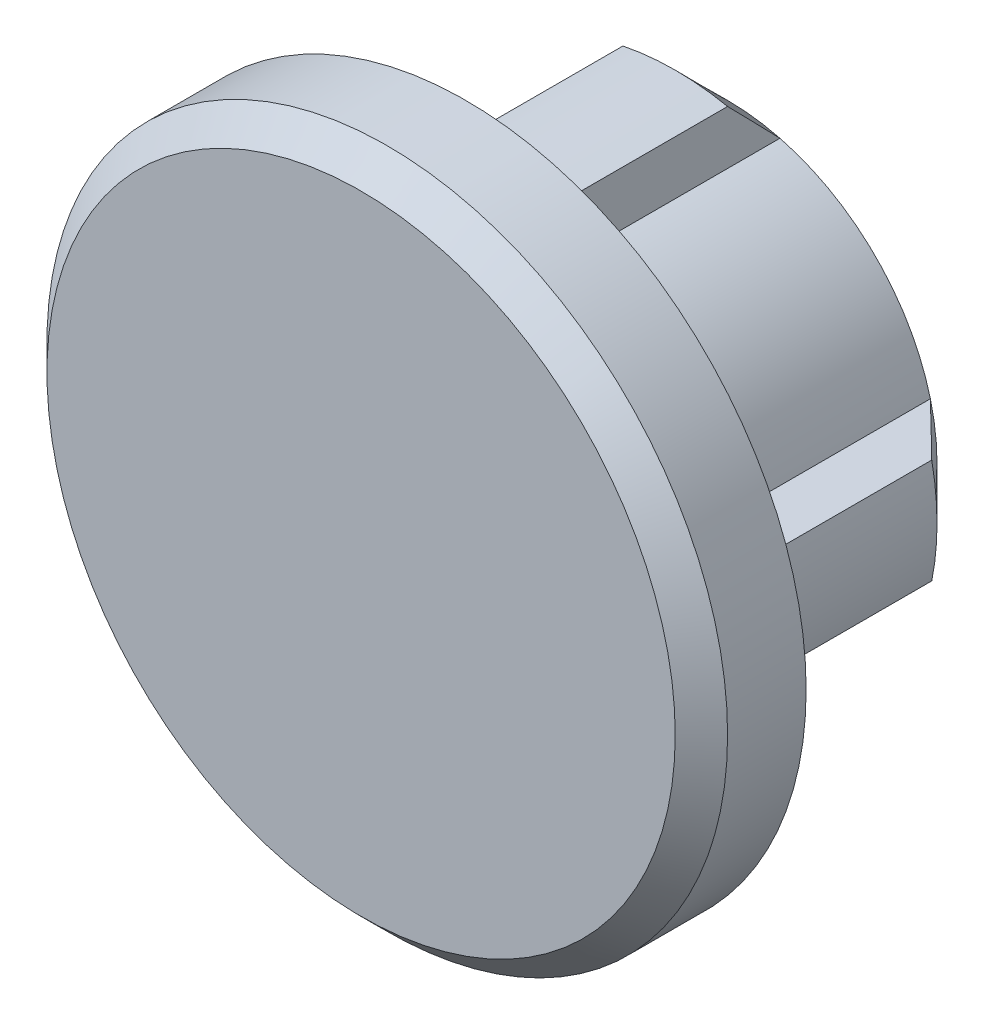
SolidWorks part; units mm, degrees
ref_plane "Front Plane" through (0, 0, 0) normal (0, 0, 1) x (1, 0, 0)
ref_plane "Top Plane" through (0, 0, 0) normal (0, 1, 0) x (1, 0, 0)
ref_plane "Right Plane" through (0, 0, 0) normal (1, 0, 0) x (0, 0, -1)
sketch "Sketch1" plane through (0, 0, 0) normal (0, 0, 1) x (1, 0, 0)
  circle A0 centre (0, 0) radius 2.5
  circle A1 centre (0, 0) radius 5
  dimension "D1" = 10
  dimension "D2" = 5
extrude "Boss-Extrude1" add sketch "Sketch1" against normal blind 5
sketch "Sketch2" plane through (0, 0, 0) normal (0, 0, 1) x (1, 0, 0)
  circle A0 centre (0, 0) radius 6.5
  dimension "D1" = 13
extrude "Boss-Extrude2" add sketch "Sketch2" along normal blind 2
chamfer "Chamfer1" distance 0.5 angle 45 1 edges at (6.5, 0, 2)
sketch "Sketch3" plane through (0, 0, 0) normal (0, 0, -1) x (-1, 0, 0)
  line L0 (3.85, 0) -> (-3.85, 0) construction
  line L1 (4.5826, 2) -> (6.1847, 2)
  line L3 (4.5826, -2) -> (6.1847, -2)
  circle A0 centre (0, 0) radius 5 construction
  circle A1 centre (0, 0) radius 6.5 construction
  circle A2 centre (0, 0) radius 5 construction
  arc A3 (6.1847, -2) -> (6.1847, 2) centre (0, 0) ccw
  arc A4 (4.5826, -2) -> (4.5826, 2) centre (0, 0) ccw
  dimension "D1" = 4
  dimension "D2" = 2
extrude "Cut-Extrude1" cut sketch "Sketch3" against normal blind 0.5
sketch "Sketch4" plane through (0, 0, -5) normal (0, 0, -1) x (-1, 0, 0)
  line L0 (3.85, 0) -> (-3.85, 0) construction
  line L2 (-1, 4.899) -> (-1, 3.873)
  line L4 (1, 4.899) -> (1, 3.873)
  line L5 (4.899, 1) -> (3.873, 1)
  line L7 (4.899, -1) -> (3.873, -1)
  line L9 (0, 3.85) -> (0, -3.85) construction
  line L11 (-3.873, 1) -> (-4.899, 1)
  line L12 (-3.873, -1) -> (-4.899, -1)
  line L13 (-1, -3.873) -> (-1, -4.899)
  line L14 (1, -3.873) -> (1, -4.899)
  arc A0 (4.5826, 2) -> (4.5826, -2) centre (0, 0) ccw construction
  arc A1 (4.899, 1) -> (1, 4.899) centre (0, 0) ccw
  arc A2 (-1, 3.873) -> (-3.873, 1) centre (0, 0) ccw
  arc A3 (3.9787, 0.4124) -> (3.9983, 0.1151) centre (0, 0) ccw construction
  arc A4 (-1, 4.899) -> (-4.899, 1) centre (0, 0) ccw
  arc A5 (4.9734, 0.5155) -> (4.9979, 0.1439) centre (0, 0) ccw construction
  arc A6 (-3.873, -1) -> (-1, -3.873) centre (0, 0) ccw
  arc A7 (-4.899, -1) -> (-1, -4.899) centre (0, 0) ccw
  arc A8 (1, -3.873) -> (3.873, -1) centre (0, 0) ccw
  arc A9 (1, -4.899) -> (4.899, -1) centre (0, 0) ccw
  arc A12 (3.873, 1) -> (1, 3.873) centre (0, 0) ccw
  dimension "D1" = 2
  dimension "D2" = 1
  dimension "D3" = 2
  dimension "D4" = 1
  dimension "D5" = 1
extrude "Cut-Extrude2" cut sketch "Sketch4" against normal up to surface (5 mm away) up to face at (0.1832, 0, 0)
chamfer "Chamfer2" distance 1 angle 45 3 edges at (-5, 0, -5) (5, 0, -5) (0, -5, -5)
